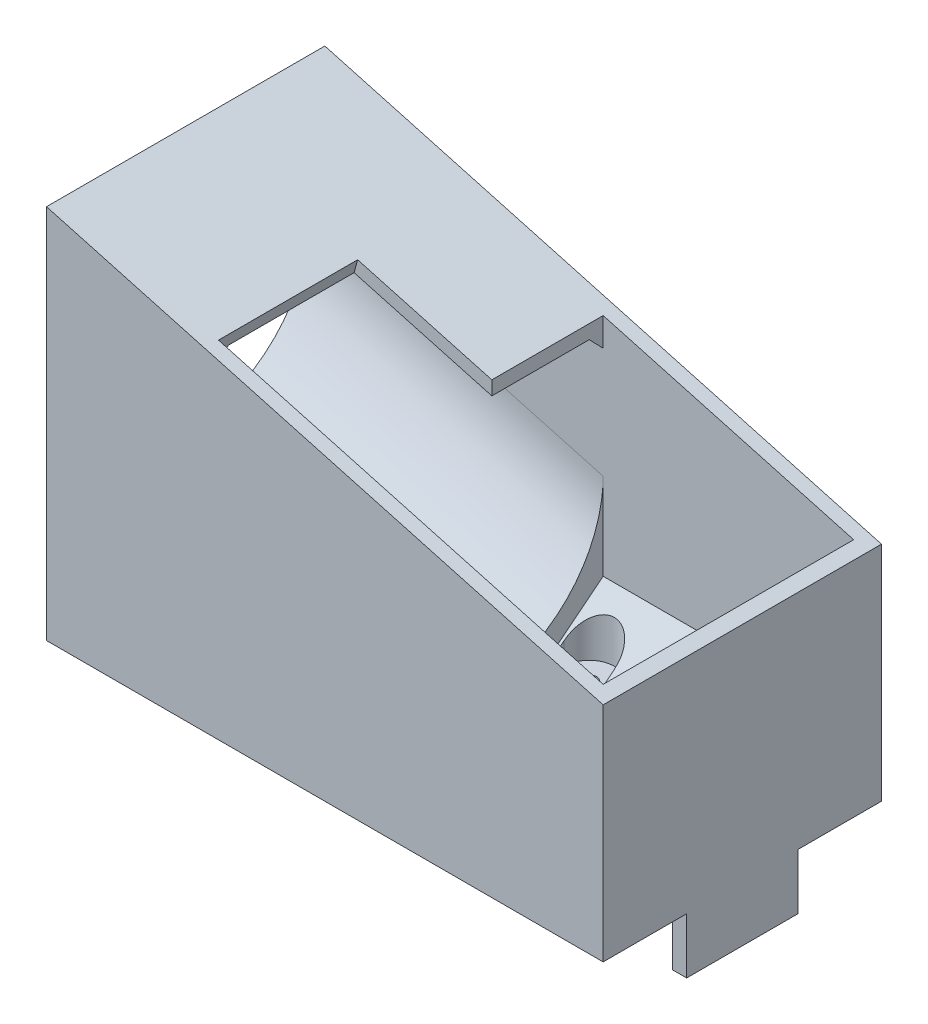
SolidWorks part; units mm, degrees
ref_plane "前视基准面" through (0, 0, 0) normal (0, 0, 1) x (1, 0, 0)
ref_plane "上视基准面" through (0, 0, 0) normal (0, 1, 0) x (1, 0, 0)
ref_plane "右视基准面" through (0, 0, 0) normal (1, 0, 0) x (0, 0, -1)
sketch "草图1" plane through (0, 0, 0) normal (0, 0, 1) x (1, 0, 0)
  line L0 (0, 0) -> (0, -20)
  line L1 (0, -20) -> (100, -20)
  line L2 (100, -20) -> (100, 0)
  line L3 (100, 0) -> (100, 100)
  line L4 (100, 100) -> (-100, 155)
  line L5 (-100, 155) -> (-100, 0)
  line L6 (-100, 0) -> (0, 0)
  line L7 (100, 0) -> (-100, 55)
  dimension "D1" = 100
  dimension "D2" = 100
  dimension "D3" = 100
  dimension "D4" = 20
  dimension "D5" = 20
  dimension "D6" = 155
extrude "凸台-拉伸1" add sketch "草图1" along normal blind 100 contours L7 L3 L4 L5 | L2 L7 L5 L6 L0 L1 region at (-11.1111, 10.7778, 0) region at (0, 77.5, 0)
sketch "草图2" plane through (0, -20, 0) normal (0, -1, 0) x (1, 0, 0)
  line L0 (0, 100) -> (0, 0) construction
  line L1 (5, 70) -> (95, 70)
  line L2 (5, 70) -> (5, 30)
  line L3 (5, 30) -> (95, 30)
  line L4 (95, 70) -> (95, 30)
  line L5 (0, 100) -> (100, 100) construction
  dimension "D1" = 90
  dimension "D2" = 5
  dimension "D3" = 40
  dimension "D4" = 30
extrude "切除-拉伸1" cut sketch "草图2" against normal through all
sketch "草图3" plane through (-100, 0, 0) normal (-1, 0, 0) x (0, 0, 1)
  line L0 (100, 155) -> (100, 0) construction
  line L1 (100, 155) -> (0, 155) construction
  circle A0 centre (50, 105) radius 45
  dimension "D3" = 90
  dimension "D1" = 50
  dimension "D2" = 50
sketch "草图4" plane through (0, 0, 0) normal (0, 0, -1) x (-1, 0, 0)
  line L0 (100, 105) -> (-59.6804, 61.0879)
  line L3 (100, 60) -> (100, 150) construction
sweep "切除-扫描1" cut profiles "草图3" path "草图4"
sketch "草图5" plane through (32.5973, 118.5357, 0) normal (0.2652, 0.9642, 0) x (0.9642, -0.2652, 0)
  line L0 (-28.6218, -45) -> (-5.9205, -45)
  line L1 (69.9049, 0) -> (-137.5198, 0) construction
  line L2 (-5.9205, -45) -> (-5.9205, -70)
  line L3 (-28.6218, -45) -> (-78.6218, -45)
  line L4 (-78.6218, -95) -> (-78.6218, -45)
  line L5 (64.7193, -70) -> (-28.6218, -70) construction
  line L6 (-78.6218, -95) -> (-5.9205, -95)
  line L8 (-5.9205, -95) -> (-5.9205, -70)
  dimension "D1" = 50
  dimension "D2" = 50
  dimension "D3" = 45
extrude "切除-拉伸2" cut sketch "草图5" against normal blind 20
sketch "草图6" plane through (0, -20, 0) normal (0, -1, 0) x (1, 0, 0)
  line L1 (100, 100) -> (0, 100)
  line L2 (100, 100) -> (100, 0)
  line L3 (100, 0) -> (0, 0)
  line L4 (0, 100) -> (0, 0)
extrude "切除-拉伸3" cut sketch "草图6" against normal blind 20
ref_plane "基准面1" through (0, 25, 0) normal (0, 1, 0) x (1, 0, 0)
sketch "草图7" plane through (0, 25, 0) normal (0, 1, 0) x (1, 0, 0)
  line L0 (-100, 0) -> (100, 0) construction
  line L1 (5, -95) -> (95, -95)
  line L2 (5, -95) -> (5, -5)
  line L3 (5, -5) -> (95, -5)
  line L4 (95, -95) -> (95, -5)
  line L6 (100, 0) -> (100, -100) construction
  dimension "D1" = 90
  dimension "D2" = 90
  dimension "D3" = 5
  dimension "D4" = 5
extrude "切除-拉伸4" cut sketch "草图7" along normal through all
sketch "草图8" plane through (0, 25, 0) normal (0, 1, 0) x (1, 0, 0)
  line L0 (5, -70) -> (5, -95) construction
  line L1 (95, -95) -> (95, -70) construction
  line L3 (95, -70) -> (59.6804, -70) construction
  circle A0 centre (15, -80) radius 2.6
  circle A1 centre (85, -80) radius 2.6
  circle A2 centre (15, -20) radius 2.6
  circle A3 centre (85, -20) radius 2.6
  dimension "D1" = 5.2
  dimension "D2" = 5.2
  dimension "D3" = 10
  dimension "D4" = 10
  dimension "D5" = 10
  dimension "D6" = 10
  dimension "D7" = 2
extrude "切除-拉伸5" cut sketch "草图8" against normal blind 20
sketch "草图9" plane through (-100, 0, 0) normal (-1, 0, 0) x (0, 0, 1)
  line L0 (100, 155) -> (0, 155) construction
  line L1 (5, 150) -> (95, 150)
  line L2 (5, 150) -> (5, 105)
  line L3 (5, 105) -> (95, 105)
  line L4 (95, 150) -> (95, 105)
  line L5 (0, 155) -> (0, 0) construction
  dimension "D1" = 45
  dimension "D2" = 90
  dimension "D3" = 5
  dimension "5" = 5
sketch "草图10" plane through (0, 0, 0) normal (0, 0, -1) x (-1, 0, 0)
  line L0 (100, 105) -> (-53.3272, 62.835)
  line L1 (100, 150) -> (100, 105) construction
sweep "切除-扫描2" cut profiles "草图9" path "草图10"
chamfer "倒角1" distance 5 angle 45 2 edges at (-72.2443, 142.3672, 95) (-47.5, 135.5625, 5)
sketch "草图11" plane through (100, 0, 0) normal (1, 0, 0) x (0, 0, -1)
  line L0 (-5, 25) -> (-5, 45)
  line L1 (55, 25) -> (-55, 25) construction
  line L2 (-5, 45) -> (-30, 25)
  line L3 (-30, 25) -> (-5, 25)
  line L4 (-70, 25) -> (-95, 45)
  line L5 (-95, 45) -> (-95, 25)
  line L6 (-95, 25) -> (-70, 25)
  line L7 (-100, 0) -> (-100, 100) construction
  line L8 (0, 0) -> (0, 100) construction
  dimension "D1" = 20
  dimension "D2" = 25
  dimension "D3" = 95
  dimension "D4" = 95
  dimension "D5" = 25
  dimension "D6" = 20
extrude "凸台-拉伸2" add sketch "草图11" against normal blind 100
sketch "草图12" plane through (0, 25, 0) normal (0, 1, 0) x (1, 0, 0)
  line L0 (95, -30) -> (59.6804, -30) construction
  line L2 (6, -20) -> (24, -20)
  line L3 (6, -20) -> (6, -33.9979)
  line L4 (6, -33.9979) -> (24, -33.9979)
  line L5 (24, -20) -> (24, -33.9979)
  line L6 (76, -20) -> (94.6849, -20)
  line L7 (76, -20) -> (76, -33.9979)
  line L8 (76, -33.9979) -> (94.6849, -33.9979)
  line L9 (94.6849, -20) -> (94.6849, -33.9979)
  line L11 (24, -80) -> (6, -80)
  line L12 (24, -80) -> (24, -64.4658)
  line L13 (24, -64.4658) -> (6, -64.4658)
  line L14 (6, -80) -> (6, -64.4658)
  line L15 (76, -80) -> (94, -80)
  line L16 (76, -80) -> (76, -65.7187)
  line L17 (76, -65.7187) -> (94, -65.7187)
  line L18 (94, -80) -> (94, -65.7187)
  circle A0 centre (15, -20) radius 9
  circle A1 centre (85, -20) radius 9
  circle A2 centre (85, -20) radius 2.6 construction
  circle A3 centre (15, -80) radius 9
  circle A4 centre (15, -20) radius 2.6 construction
  circle A5 centre (85, -80) radius 9
  dimension "D1" = 18
  dimension "D2" = 18
  dimension "D5" = 0
  dimension "D6" = 0
  dimension "D3" = 10
  dimension "D4" = 10
  dimension "D7" = 2
extrude "切除-拉伸6" cut sketch "草图12" along normal blind 130 contours L2 A0 | A0 L3 L4 L5 | L2 A0 | L6 A1 | L6 A1 | A1 L7 L8 L9 L6 | A3 L12 L13 L14 | L11 A3 | L11 A3 | A5 L18 L17 L16 | L15 A5 | L15 A5 region at (15, 25, 16.1803) region at (15, 25, 30.2421) region at (15, 25, 23.8197) region at (85, 25, 16.1803) region at (85.6668, 25, 30.0106) region at (85, 25, 23.8197) region at (15, 25, 83.8197) region at (15, 25, 68.937) region at (15, 25, 76.1803) region at (85, 25, 76.1803) region at (85, 25, 69.6048) region at (85, 25, 83.8197)
sketch "草图13" plane through (-100, 0, 0) normal (-1, 0, 0) x (0, 0, 1)
  line L1 (100, 0) -> (0, 0) construction
  line L2 (-4.9765, 20) -> (-4.9765, -2.9956)
  line L3 (-4.9765, -2.9956) -> (106.6812, -2.9956)
  line L4 (106.6812, 20) -> (106.6812, -2.9956)
  line L5 (-4.9765, 20) -> (106.6812, 20)
  dimension "D1" = 20
extrude "切除-拉伸7" cut sketch "草图13" against normal blind 100
sketch "草图14" plane through (100, 0, 0) normal (1, 0, 0) x (0, 0, -1)
  line L1 (-30, 20) -> (11.7913, 20)
  line L2 (-30, 20) -> (-30, -3.6238)
  line L3 (-30, -3.6238) -> (11.7913, -3.6238)
  line L4 (11.7913, 20) -> (11.7913, -3.6238)
  line L5 (-100, 0) -> (-100, 100) construction
  line L6 (-111.641, 20) -> (-70, 20)
  line L7 (-70, 20) -> (-70, -3.1298)
  line L8 (-70, -3.1298) -> (-111.641, -3.1298)
  line L9 (-111.641, 20) -> (-111.641, -3.1298)
  line L10 (0, 0) -> (0, 100) construction
  line L12 (0, 0) -> (-100, 0) construction
  dimension "D1" = 30
  dimension "D2" = 30
  dimension "D3" = 20
extrude "切除-拉伸8" cut sketch "草图14" against normal blind 100
